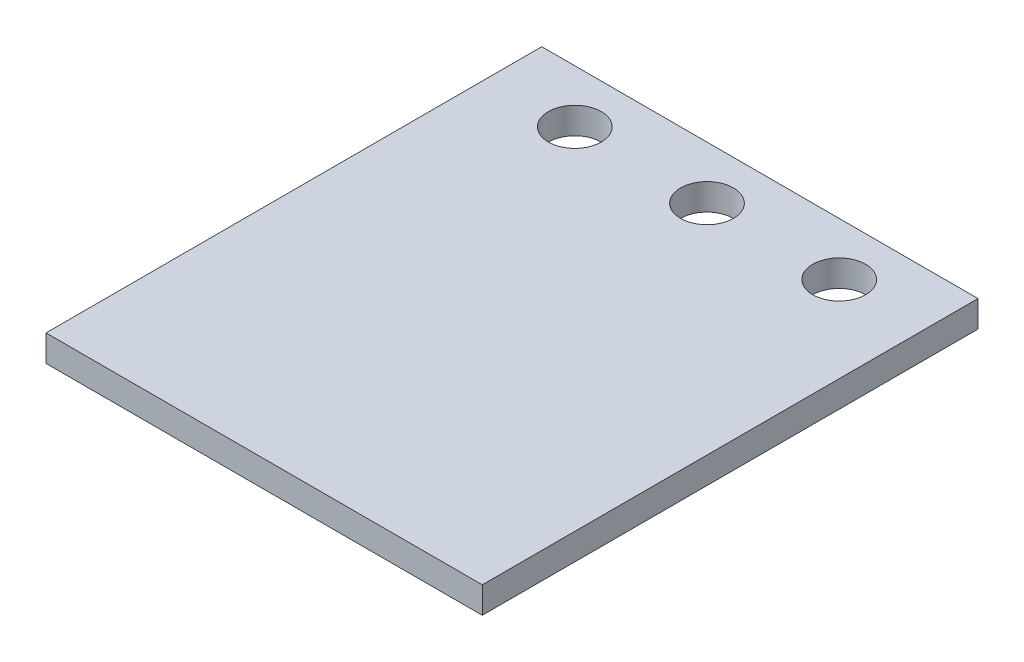
SolidWorks part; units mm, degrees
ref_plane "Alzado" through (0, 0, 0) normal (0, 0, 1) x (1, 0, 0)
ref_plane "Planta" through (0, 0, 0) normal (0, 1, 0) x (1, 0, 0)
ref_plane "Vista lateral" through (0, 0, 0) normal (1, 0, 0) x (0, 0, -1)
ref_plane "Plano1" through (0, 0, 360) normal (0, 0, -1) x (-1, 0, 0)
sketch "Croquis2" plane through (0, 0, 360) normal (0, 0, -1) x (-1, 0, 0)
  line L0 (7.7541, 182.0598) -> (7.7541, 202.8344) construction
  line L1 (192.7541, 202.8344) -> (-177.2459, 202.8344) construction
  line L2 (7.7541, 202.8344) -> (7.7541, 222.538) construction
  line L3 (-157.2459, 202.8344) -> (172.7541, 202.8344)
  line L4 (-157.2459, 202.8344) -> (-157.2459, 182.8344)
  line L5 (-157.2459, 182.8344) -> (172.7541, 182.8344)
  line L6 (172.7541, 202.8344) -> (172.7541, 182.8344)
  point P4 (7.7541, 182.0598)
  dimension "D1" = 330
  dimension "D2" = 20
extrude "Saliente-Extruir1" add sketch "Croquis2" along normal blind 375
sketch "Croquis3" plane through (0, 202.8344, 0) normal (0, 1, 0) x (1, 0, 0)
  line L0 (-7.7541, 15) -> (-7.7541, -25) construction
  line L1 (-172.7541, 15) -> (157.2459, 15) construction
  circle A0 centre (-107.7541, -25) radius 20
  circle A1 centre (-7.7541, -25) radius 20
  circle A2 centre (92.2459, -25) radius 20
  point P7 (-7.7541, -5)
  dimension "D3" = 40
  dimension "D1" = 20
  dimension "D4" = 100
  dimension "D2" = 3
extrude "Cortar-Extruir1" cut sketch "Croquis3" against normal up to next
